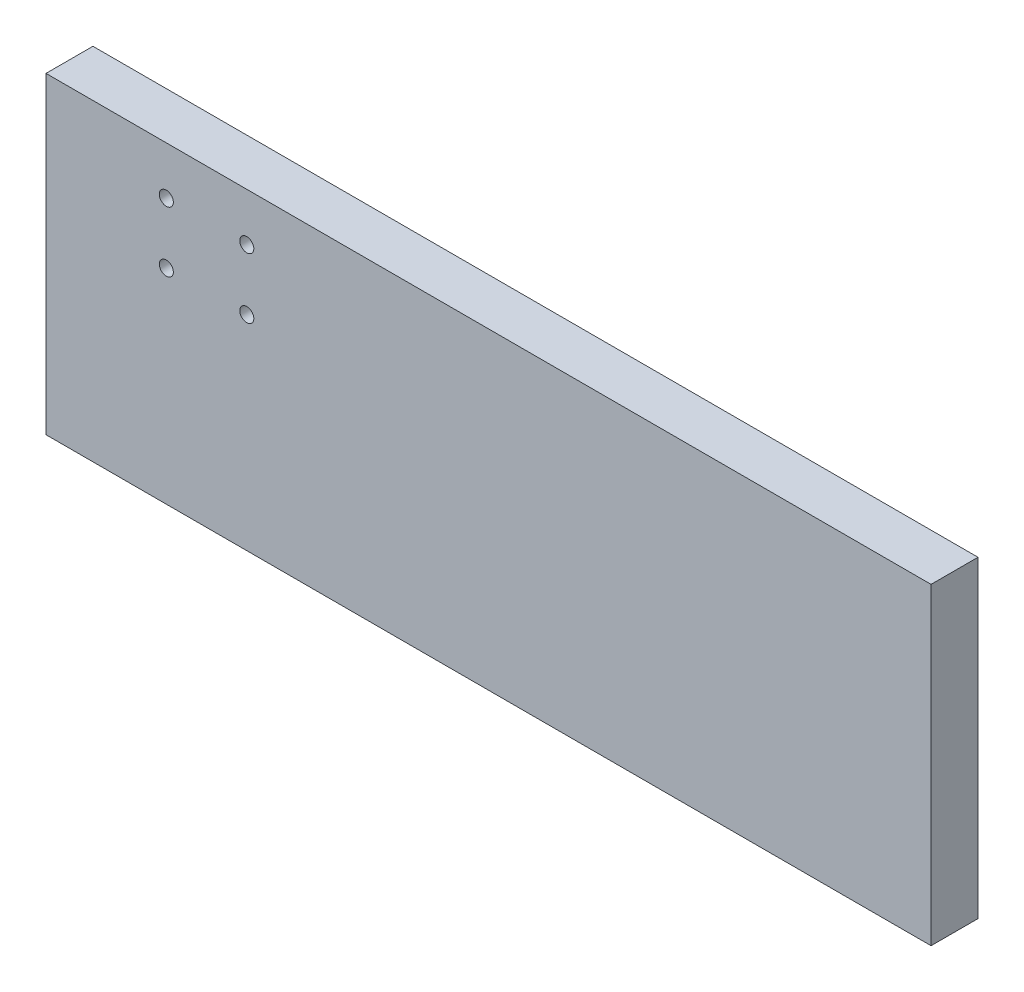
SolidWorks part; units mm, degrees
ref_plane "Front Plane" through (0, 0, 0) normal (0, 0, 1) x (1, 0, 0)
ref_plane "Top Plane" through (0, 0, 0) normal (0, 1, 0) x (1, 0, 0)
ref_plane "Right Plane" through (0, 0, 0) normal (1, 0, 0) x (0, 0, -1)
sketch "Sketch1" plane through (0, 0, 0) normal (0, 0, 1) x (1, 0, 0)
  line L1 (0, 0) -> (359.156, 0)
  line L2 (0, 0) -> (0, 127)
  line L3 (0, 127) -> (359.156, 127)
  line L4 (359.156, 0) -> (359.156, 127)
  dimension "D1" = 127
  dimension "D2" = 359.156
extrude "Boss-Extrude1" add sketch "Sketch1" along normal blind 19.05
sketch "Sketch2" plane through (0, 0, 19.05) normal (0, 0, 1) x (1, 0, 0)
  circle A0 centre (48.8251, 82.9627) radius 2.8511
  circle A1 centre (48.8251, 107.5372) radius 2.8511
  circle A2 centre (81.4768, 107.5372) radius 2.8512
  circle A3 centre (81.4768, 82.9627) radius 2.8512
extrude "Cut-Extrude1" cut sketch "Sketch2" against normal up to next
sketch "Sketch3" plane through (0, 0, 0) normal (0, 0, -1) x (-1, 0, 0)
  line L0 (-65.151, 114.3) -> (-65.151, 117.475) construction
  line L1 (-58.6607, 114.3) -> (-71.6413, 114.3) construction
  circle A1 centre (-65.151, 117.475) radius 3.175
  dimension "D1" = 3.175
  dimension "D2" = 6.35
extrude "Cut-Extrude2" cut sketch "Sketch3" against normal blind 6.35
